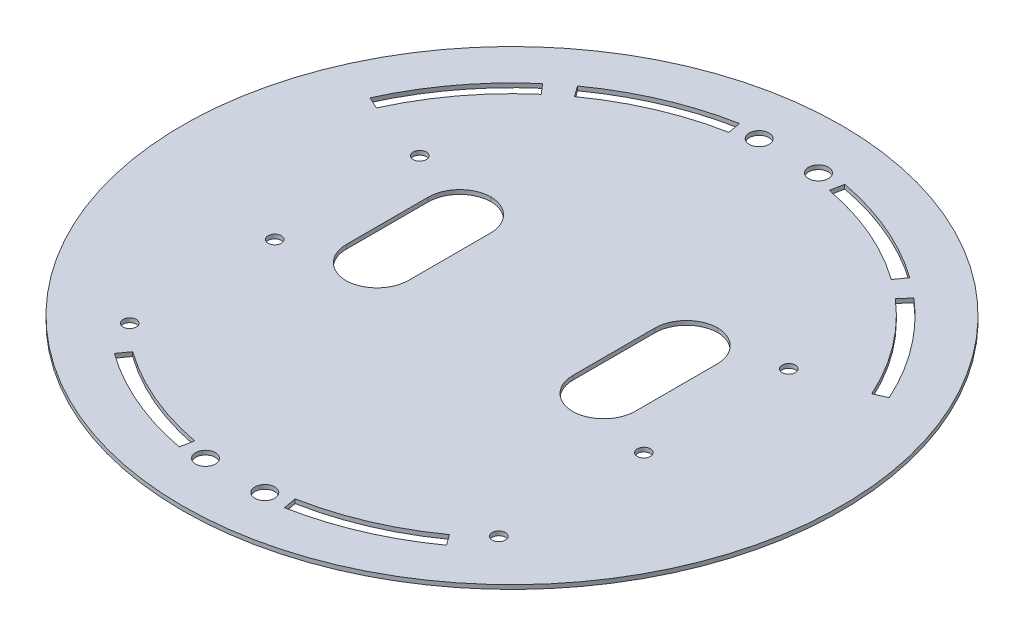
SolidWorks part; units mm, degrees
ref_plane "Front Plane" through (0, 0, 0) normal (0, 0, 1) x (1, 0, 0)
ref_plane "Top Plane" through (0, 0, 0) normal (0, 1, 0) x (1, 0, 0)
ref_plane "Right Plane" through (0, 0, 0) normal (1, 0, 0) x (0, 0, -1)
sketch "Sketch1" plane through (0, 0, 0) normal (0, 1, 0) x (1, 0, 0)
  line L0 (0, 0) -> (0, -79.375)
  line L1 (7.1438, -66.675) -> (-7.1437, -66.675)
  line L2 (50.8, 22.225) -> (76.2, 22.225)
  line L3 (-63.5, -47.625) -> (-50.8, -47.625)
  line L4 (-50.8, -47.625) -> (-50.8, 22.225)
  line L5 (63.5, -47.625) -> (50.8, -47.625)
  line L6 (50.8, -47.625) -> (50.8, 22.225)
  line L7 (-50.8, 22.225) -> (-76.2, 22.225)
  line L8 (0, 0) -> (-27.2811, 0)
  circle A0 centre (0, 0) radius 79.375
  circle A1 centre (-7.1437, -66.675) radius 1.5875
  circle A2 centre (7.1438, -66.675) radius 1.5875
  circle A3 centre (7.1438, 66.675) radius 1.5875
  circle A4 centre (-7.1437, 66.675) radius 1.5875
  point P7 (0, -66.675)
  dimension "D1" = 7.1437
  dimension "D3" = 50.8
  dimension "D6" = 3.175
  dimension "D2" = 12.7
  dimension "D4" = 69.85
  dimension "D5" = 47.625
extrude "Boss-Extrude5" add sketch "Sketch1" along normal blind 1.5875 contours A2 A0 L5 L6 L2 L7 L4 L3 A1 A3 region at (0, 0, -2.0947)
fillet "Fillet2" radius 2.54 1 edges at (-63.5, 0.7937, 47.625)
fillet "Fillet3" radius 2.54 1 edges at (63.5, 0.7937, 47.625)
fillet "Fillet4" radius 5.08 2 edges at (-76.2, 0.7937, -22.225) (76.2, 0.7937, -22.225)
sketch "Sketch2" plane through (0, 1.5875, 0) normal (0, 1, 0) x (1, 0, 0)
  line L0 (0, 0) -> (0, 79.375)
  line L1 (0, 0) -> (-67.0566, 0)
  line L2 (0, 0) -> (-61.0886, 27.6545)
  line L3 (0, 0) -> (-43.6778, 50.8806)
  line L4 (0, 0) -> (-63.2664, 22.225)
  line L5 (-50.8, 22.225) -> (-69.0955, 22.225) construction
  line L6 (0, 0) -> (0, 2.6153)
  line L7 (0, 0) -> (-39.0771, 54.4938)
  line L8 (0, 0) -> (-12.3858, 65.9028)
  line L9 (-62.5348, 28.3092) -> (-59.6424, 26.9998)
  line L10 (-43.6778, 50.8806) -> (-44.7118, 52.0852)
  line L11 (-43.6778, 50.8806) -> (-42.6438, 49.6761)
  line L12 (-39.0771, 54.4938) -> (-40.0022, 55.7839)
  line L13 (-39.0771, 54.4938) -> (-38.152, 53.2037)
  line L14 (-43.6778, 50.8806) -> (-42.6438, 49.6761)
  line L15 (-12.3858, 65.9028) -> (-12.0926, 64.3426)
  line L16 (-12.3858, 65.9028) -> (-12.679, 67.463)
  line L17 (61.5813, 22.225) -> (64.9466, 22.225)
  line L18 (50.8, 22.225) -> (69.0955, 22.225) construction
  line L19 (12.3858, 65.9028) -> (12.679, 67.463)
  line L20 (12.3858, 65.9028) -> (12.0926, 64.3426)
  line L21 (39.0771, 54.4938) -> (38.152, 53.2037)
  line L22 (43.6778, 50.8806) -> (42.6438, 49.6761)
  line L23 (39.0771, 54.4938) -> (40.0022, 55.7839)
  line L24 (43.6778, 50.8806) -> (42.6438, 49.6761)
  line L25 (43.6778, 50.8806) -> (44.7118, 52.0852)
  line L26 (62.5348, 28.3092) -> (59.6424, 26.9998)
  line L27 (-50.8, -41.2985) -> (-50.8, -43.7716)
  line L28 (-50.8, -47.625) -> (-50.8, 22.225) construction
  line L29 (50.8, -41.2985) -> (50.8, -46.1668)
  line L30 (50.8, -47.625) -> (50.8, 22.225) construction
  line L31 (39.0771, -54.4938) -> (40.0022, -55.7839)
  line L32 (39.0771, -54.4938) -> (38.152, -53.2037)
  line L33 (12.3858, -65.9028) -> (12.0926, -64.3426)
  line L34 (12.3858, -65.9028) -> (12.679, -67.463)
  line L35 (-12.3858, -65.9028) -> (-12.679, -67.463)
  line L36 (-12.3858, -65.9028) -> (-12.0926, -64.3426)
  line L37 (-39.0771, -54.4938) -> (-38.152, -53.2037)
  line L38 (-39.0771, -54.4938) -> (-40.0022, -55.7839)
  arc A0 (-63.2664, 22.225) -> (-50.8, -43.7716) centre (0, 0) ccw
  arc A1 (73.8199, 29.172) -> (-73.8199, 29.172) centre (0, 0) ccw construction
  circle A2 centre (-7.1437, 66.675) radius 2.3813
  circle A3 centre (7.1437, 66.675) radius 2.3813
  circle A4 centre (7.1437, -66.675) radius 2.3813
  circle A5 centre (-7.1437, -66.675) radius 2.3813
  arc A6 (12.679, -67.463) -> (40.0022, -55.7839) centre (0, 0) ccw
  arc A7 (-61.7686, 21.6988) -> (-50.8, -41.2985) centre (0, 0) ccw
  arc A8 (-44.7118, 52.0852) -> (-62.5348, 28.3092) centre (0, 0) ccw
  arc A9 (-42.6438, 49.6761) -> (-59.6424, 26.9998) centre (0, 0) ccw
  arc A10 (12.0926, 64.3426) -> (38.152, 53.2037) centre (0, 0) cw
  arc A11 (12.679, 67.463) -> (40.0022, 55.7839) centre (0, 0) cw
  arc A12 (42.6438, 49.6761) -> (59.6424, 26.9998) centre (0, 0) cw
  arc A13 (-12.679, 67.463) -> (-40.0022, 55.7839) centre (0, 0) ccw
  arc A14 (44.7118, 52.0852) -> (62.5348, 28.3092) centre (0, 0) cw
  arc A15 (-12.0926, 64.3426) -> (-38.152, 53.2037) centre (0, 0) ccw
  arc A16 (12.0926, -64.3426) -> (38.152, -53.2037) centre (0, 0) ccw
  arc A17 (-12.0926, -64.3426) -> (-38.152, -53.2037) centre (0, 0) cw
  arc A18 (50.8, -46.1668) -> (64.9466, 22.225) centre (0, 0) ccw
  arc A19 (50.8, -43.7716) -> (63.2664, 22.225) centre (0, 0) ccw
  arc A20 (50.8, -41.2985) -> (61.5813, 22.225) centre (0, 0) ccw
  arc A21 (-12.679, -67.463) -> (-40.0022, -55.7839) centre (0, 0) cw
  circle M13 centre (-7.1437, -66.675) radius 1.5875
  circle M14 centre (7.1438, -66.675) radius 1.5875
  circle M15 centre (7.1438, 66.675) radius 1.5875
  circle M16 centre (-7.1437, 66.675) radius 1.5875
  dimension "D2" = 4.7625
  dimension "D7" = 1.5875
  dimension "D8" = 3.175
  dimension "D1" = 5
  dimension "D3" = 25
  dimension "D4" = 5
  dimension "D5" = 25
extrude "Cut-Extrude1" cut sketch "Sketch2" against normal blind 2.54 contours A9 L3 L10 A8 L9 L2 | A15 L8 L16 A13 L12 L7 | A2 M16 | A3 M15 | A11 L19 L20 A10 L21 L23 | A14 L25 L22 A12 L26 | A21 L35 L36 A17 L37 L38 | A5 M13 | A4 M14 | A16 L33 L34 A6 L31 L32 region at (-53.2404, 1.5875, -39.9101) region at (-26.1525, 1.5875, -61.1833) region at (26.1525, 1.5875, -61.1833) region at (53.2404, 1.5875, -39.9101) region at (26.1525, 1.5875, 61.1833) region at (-26.1525, 1.5875, 61.1833) region at (-9.4576, 1.5875, -66.675) region at (4.8299, 1.5875, -66.675) region at (4.8299, 1.5875, 66.675) region at (-9.4576, 1.5875, 66.675)
sketch "Sketch3" plane through (0, 1.5875, 0) normal (0, 1, 0) x (1, 0, 0)
  line L0 (-50.8, 22.225) -> (-50.8, -47.625)
  line L1 (-50.8, -47.625) -> (-44.45, -47.625)
  line L2 (-50.8, 22.225) -> (-44.45, 22.225)
  line L3 (0, 0) -> (0, 32.9013)
  circle A0 centre (-44.45, -47.625) radius 1.5875
  circle A1 centre (-44.45, 22.225) radius 1.5875
  circle A2 centre (44.45, 22.225) radius 1.5875
  circle A3 centre (44.45, -47.625) radius 1.5875
  dimension "D2" = 3.175
  dimension "D4" = 3.175
  dimension "D1" = 6.35
  dimension "D3" = 6.35
extrude "Cut-Extrude2" cut sketch "Sketch3" against normal blind 2.54 contours A1 | A2 | A0 | A3 region at (-44.45, 1.5875, 46.0824) region at (-44.45, 1.5875, -23.7676) region at (44.45, 1.5875, -22.225) region at (44.45, 1.5875, 47.625)
sketch "Sketch4" plane through (0, 1.5875, 0) normal (0, 1, 0) x (1, 0, 0)
  line L0 (-44.45, -47.625) -> (-44.45, 22.225)
  line L1 (-44.45, 22.225) -> (-50.8, 22.225)
  line L2 (-50.8, -47.625) -> (-50.8, 22.225) construction
  line L3 (0, 0) -> (0, -67.5878)
  line L4 (44.45, -47.625) -> (44.45, 22.225)
  circle A0 centre (-44.45, 22.225) radius 1.5875
  circle A1 centre (-44.45, -12.7) radius 1.5875
  circle A2 centre (44.45, -12.7) radius 1.5875
  dimension "D2" = 3.175
  dimension "D1" = 69.85
extrude "Cut-Extrude3" cut sketch "Sketch4" against normal blind 2.54 contours L0 A1 | L0 A1 | A2 L4 | A2 L4 region at (-45.1238, 1.5875, 12.7) region at (-43.7762, 1.5875, 12.7) region at (43.7762, 1.5875, 12.7) region at (45.1238, 1.5875, 12.7)
sketch "Sketch5" plane through (0, 1.5875, 0) normal (0, 1, 0) x (1, 0, 0)
  line L0 (-50.8, -12.7) -> (-34.8, -12.7)
  line L1 (-50.8, -47.625) -> (-50.8, 22.225) construction
  line L2 (-50.8, 22.225) -> (-34.8, 22.225)
  line L3 (-34.8, 22.225) -> (-34.8, -12.7)
  line L4 (0, 0) -> (0, 64.5379)
  line L5 (-34.8, 22.225) -> (-19.8, 22.225)
  line L6 (-19.8, 22.225) -> (-19.8, -12.7)
  line L7 (-19.8, -12.7) -> (-34.8, -12.7)
  line L8 (19.8, -12.7) -> (34.8, -12.7)
  line L9 (19.8, 22.225) -> (19.8, -12.7)
  line L10 (34.8, 22.225) -> (19.8, 22.225)
  line L11 (34.8, 22.225) -> (34.8, -12.7)
  dimension "D1" = 16
  dimension "D2" = 16
extrude "Cut-Extrude4" cut sketch "Sketch5" against normal through all contours L7 L6 L5 L3 | L11 L10 L9 L8 region at (-27.3, 1.5875, -4.7625) region at (27.3, 1.5875, -4.7625)
fillet "Fillet5" radius 7.62 4 edges at (-19.8, 0.7937, 12.7) (-34.8, 0.7937, 12.7) (-19.8, 0.7937, -22.225) (-34.8, 0.7937, -22.225)
fillet "Fillet6" radius 7.62 4 edges at (34.8, 0.7937, 12.7) (34.8, 0.7937, -22.225) (19.8, 0.7937, -22.225) (19.8, 0.7937, 12.7)
sketch "Sketch6" plane through (0, 1.5875, 0) normal (0, 1, 0) x (1, 0, 0)
  line L0 (-50.8, 22.225) -> (-69.0955, 22.225)
  line L1 (-69.0955, 22.225) -> (-69.0955, 39.0667)
  line L2 (-50.8, 22.225) -> (-50.8, -60.9898)
  line L3 (50.8, 22.225) -> (69.0955, 22.225)
  line L4 (69.0955, 22.225) -> (69.0955, 39.0667)
  line L5 (50.8, 22.225) -> (50.8, -60.9898)
  circle A0 centre (0, 0) radius 79.375
extrude "Boss-Extrude6" add sketch "Sketch6" against normal blind 1.5875 contours L1 A0 L2 L0 | L5 A0 L4 L3 region at (-63.4454, 1.5875, 10.5781) region at (63.4454, 1.5875, 10.5781)
sketch "Sketch7" plane through (0, 0, 0) normal (0, -1, 0) x (1, 0, 0)
  circle A0 centre (0, 0) radius 79.375
extrude "Cut-Extrude5" cut sketch "Sketch7" against normal blind 0.5875
